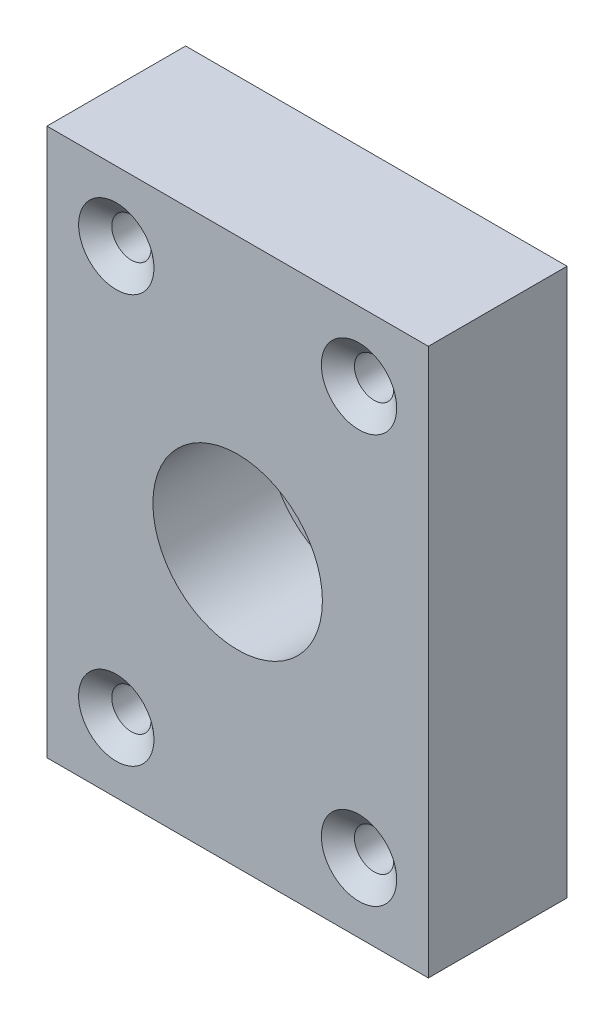
SolidWorks part; units mm, degrees
material "Beech"
ref_plane "Front Plane" through (0, 0, 0) normal (0, 0, 1) x (1, 0, 0)
ref_plane "Top Plane" through (0, 0, 0) normal (0, 1, 0) x (1, 0, 0)
ref_plane "Right Plane" through (0, 0, 0) normal (1, 0, 0) x (0, 0, -1)
sketch "Sketch1" plane through (0, 0, 0) normal (0, 0, 1) x (1, 0, 0)
  line L1 (0, 0) -> (49.5, 0)
  line L2 (0, 0) -> (0, 71)
  line L3 (0, 71) -> (49.5, 71)
  line L4 (49.5, 0) -> (49.5, 71)
  dimension "D1" = 71
  dimension "D2" = 49.5
extrude "base" add sketch "Sketch1" along normal blind 18
sketch "Sketch2" plane through (0, 0, 18) normal (0, 0, 1) x (1, 0, 0)
  line L0 (0, 71) -> (49.5, 0) construction
  line L1 (0, 0) -> (49.5, 71) construction
  circle A0 centre (24.75, 35.5) radius 11
  point P10 (0, 0)
  dimension "D1" = 22
extrude "lead nut inlay" cut sketch "Sketch2" against normal blind 15
sketch "Sketch3" plane through (0, 0, 3) normal (0, 0, 1) x (1, 0, 0)
  circle A0 centre (24.75, 35.5) radius 6.5
  circle A1 centre (24.75, 35.5) radius 11 construction
  dimension "D1" = 13
extrude "lead screw clearance" cut sketch "Sketch3" against normal through all
hole_wizard "woodscrew clearance" positions "Sketch4" profile "Sketch5" countersink size "#10" standard "ANSI Inch" end condition through all
sketch "Sketch4" plane through (0, 0, 18) normal (0, 0, 1) x (1, 0, 0)
  line L1 (9, 9) -> (40.5, 9)
  line L2 (9, 9) -> (9, 62)
  line L3 (9, 62) -> (40.5, 62)
  line L4 (40.5, 9) -> (40.5, 62)
  line L5 (24.75, 62) -> (24.75, 71)
  line L6 (49.5, 71) -> (0, 71) construction
  line L7 (9, 35.5) -> (0, 35.5)
  line L8 (0, 71) -> (0, 0) construction
  point P1 (9, 9)
  point P2 (40.5, 62)
  point P185 (9, 62)
  point P186 (40.5, 9)
  dimension "D1" = 9
sketch "Sketch5" plane through (9, 9, 18) normal (1, 0, 0) x (0, -1, 0)
  line L0 (0, 0) -> (0, 18)
  line L1 (0, 18) -> (2.5527, 18)
  line L2 (2.5527, 18) -> (2.5527, 1.9608)
  line L3 (2.5527, 1.9608) -> (4.8895, 0)
  line L5 (4.8895, 0) -> (0, 0)
  line L6 (-2.5527, 1.9608) -> (-4.8895, 0) construction
  line L11 (0, -6.35) -> (0, 107.95) construction
  dimension "Thru Hole Dia." = 5.1054
  dimension "Thru Hole Depth" = 18
  dimension "Near C'Sink Dia." = 9.779
  dimension "Near C'Sink Angle" = 100
